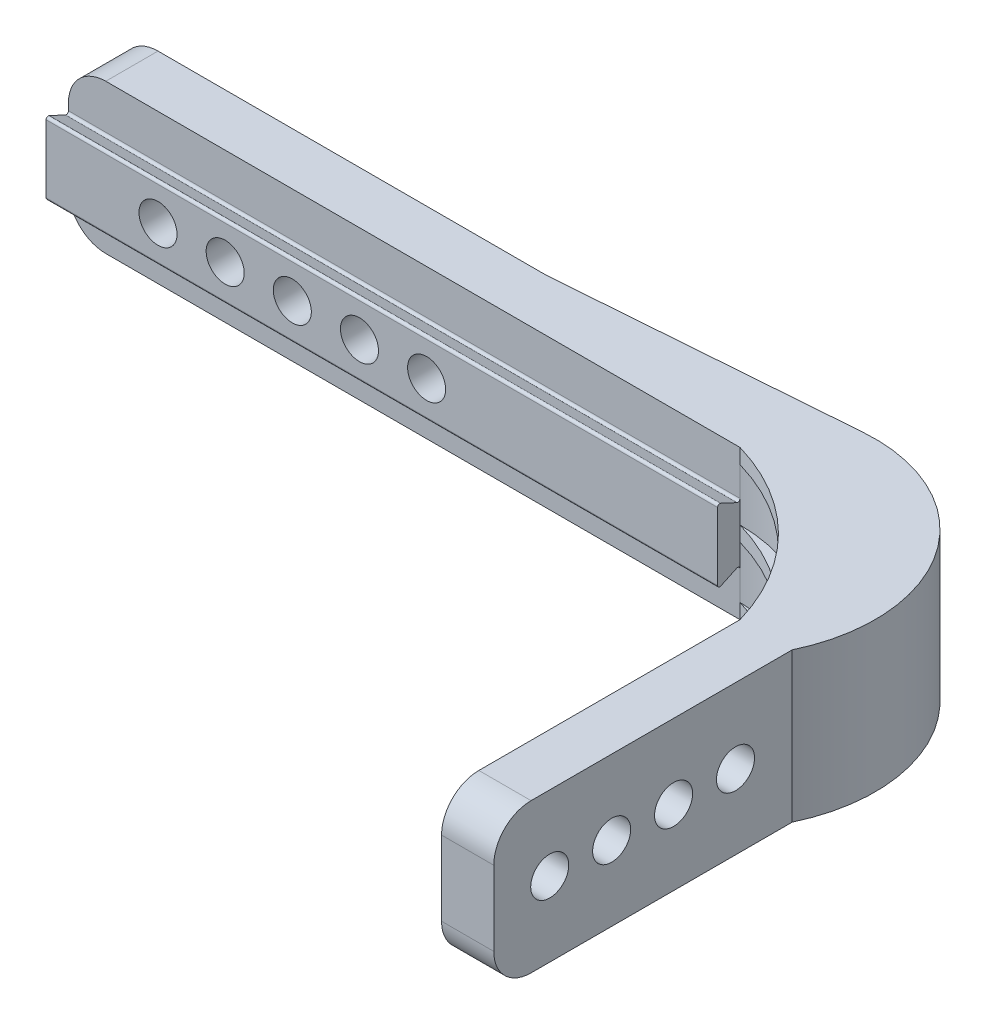
SolidWorks part; units mm, degrees
ref_plane "Front Plane" through (0, 0, 0) normal (0, 0, 1) x (1, 0, 0)
ref_plane "Top Plane" through (0, 0, 0) normal (0, 1, 0) x (1, 0, 0)
ref_plane "Right Plane" through (0, 0, 0) normal (1, 0, 0) x (0, 0, -1)
sketch "Sketch1" plane through (0, 0, 0) normal (0, 1, 0) x (1, 0, 0)
  line L0 (0, 0) -> (90, 0)
  line L1 (117, -27) -> (117, -67)
  line L2 (0, -7) -> (90, -7)
  line L3 (110, -27) -> (110, -67)
  line L4 (110, -67) -> (117, -67)
  line L5 (0, -7) -> (0, 0)
  arc A0 (90, 0) -> (117, -27) centre (90, -27) cw
  arc A1 (90, -7) -> (110, -27) centre (90, -27) cw
  dimension "D4" = 20
  dimension "D2" = 90
  dimension "D3" = 40
  dimension "D1" = 7
extrude "Boss-Extrude1" add sketch "Sketch1" along normal blind 20
sketch "Sketch2" plane through (0, 0, 0) normal (1, 0, 0) x (0, 0, -1)
  line L1 (-7, 20) -> (-7, 0) construction
  line L2 (-10, 15) -> (-10, 5)
  line L3 (-10, 5) -> (-7, 6.3989)
  line L4 (-7, 6.3989) -> (-7, 13.6011)
  line L5 (-7, 10) -> (-10, 10) construction
  line L6 (-7, 13.6011) -> (-10, 15)
  line L7 (-7, 20) -> (-27, 20) construction
  line L8 (-7, 13.6011) -> (-10, 13.6011) construction
  line L9 (-7, 6.3989) -> (-10, 6.3989) construction
  dimension "D1" = 10
  dimension "D2" = 7.2022
  dimension "D3" = 3
  dimension "D4" = 25
  dimension "D9" = 10
extrude "Boss-Extrude2" add sketch "Sketch2" along normal up to vertex (90 mm away) up to point (90, 20, 7)
ref_plane "Plane1" through (0, 0, 65) normal (0, 0, 1) x (1, 0, 0)
sketch "Sketch3" plane through (0, 0, 65) normal (0, 0, 1) x (1, 0, 0)
  line L6 (117, 12) -> (117, 8)
  line L8 (117, 20) -> (117, 0) construction
  line L9 (117, 8) -> (120, 5)
  line L10 (120, 5) -> (120, 15)
  line L11 (120, 15) -> (117, 12)
  line L12 (117, 10) -> (120, 10) construction
  line L13 (110, 20) -> (117, 20) construction
  dimension "D1" = 10
  dimension "D2" = 4
  dimension "D3" = 3
  dimension "D4" = 10
extrude "Boss-Extrude3" [suppressed] add sketch "Sketch3" against normal blind 40
sketch "Sketch4" plane through (0, 0, 0) normal (1, 0, 0) x (0, 0, -1)
  line L0 (-27, 20) -> (-67, 20) construction
  line L1 (-67, 20) -> (-67, 0) construction
  circle A0 centre (-59.5, 10) radius 2.55
  dimension "D1" = 5.1
  dimension "D2" = 10
  dimension "D3" = 7.5
extrude "Cut-Extrude1" cut sketch "Sketch4" along normal through all
pattern_linear "LPattern1" count 4 spacing 8.3 along (0, 0, -1) of "Cut-Extrude1"
sketch "Sketch5" plane through (0, 0, 0) normal (0, 0, 1) x (1, 0, 0)
  line L0 (90, 20) -> (0, 20) construction
  line L1 (0, 20) -> (0, 0) construction
  circle A0 centre (15, 10) radius 2.55
  dimension "D1" = 5.1
  dimension "D2" = 10
  dimension "D3" = 15
extrude "Cut-Extrude2" cut sketch "Sketch5" along normal blind 14
pattern_linear "LPattern2" count 5 spacing 9 along (1, 0, 0) of "Cut-Extrude2"
fillet "Fillet1" [suppressed] radius 0.5
fillet "Fillet2" radius 5 4 edges at (113.5, 0, 67) (113.5, 20, 67) (0, 0, 3.5) (0, 20, 3.5)
sketch "Sketch6" plane through (0, 0, 0) normal (0, 1, 0) x (1, 0, 0)
  line L0 (90, 0) -> (5, 0) construction
  line L1 (57.068, 0) -> (96.4605, 3)
  line L2 (90, 0) -> (57.068, 0)
  line L6 (110, -27) -> (110, -62)
  line L7 (110, -62) -> (117, -62)
  line L8 (117, -62) -> (117, -27)
  line L9 (90, 0) -> (5, 0)
  line L10 (5, 0) -> (5, -7)
  line L11 (5, -7) -> (90, -7)
  arc A0 (117, -27) -> (96.4605, 3) centre (98.0552, -17.9394) ccw
  arc A3 (117, -27) -> (90, 0) centre (90, -27) ccw
  arc A8 (117, -27) -> (90, 0) centre (90, -27) ccw
  arc A9 (110, -27) -> (90, -7) centre (90, -27) ccw
  dimension "D2" = 21
  dimension "D3" = 3
  dimension "D1" = 0
extrude "Boss-Extrude4" add sketch "Sketch6" along normal up to surface (20 mm away) up to face at (81.7168, 20, 22.7832)
sketch "Sketch8" plane through (0, 0, 0) normal (0, 1, 0) x (1, 0, 0)
  arc A0 (90, -7) -> (110, -27) centre (81.8988, -35.1012) cw
  arc A1 (90, -7) -> (110, -27) centre (90, -27) cw
extrude "Boss-Extrude5" add sketch "Sketch8" along normal blind 2
pattern_linear "LPattern3" count 3 spacing 9 along (0, 1, 0) of "Boss-Extrude5"
fillet "Fillet3" radius 0.3 4 edges at (45, 6.3989, 7) (45, 5, 10) (45, 15, 10) (45, 13.6011, 7)
fillet "Fillet4" radius 20 1 edges at (57.068, 10, 0)
